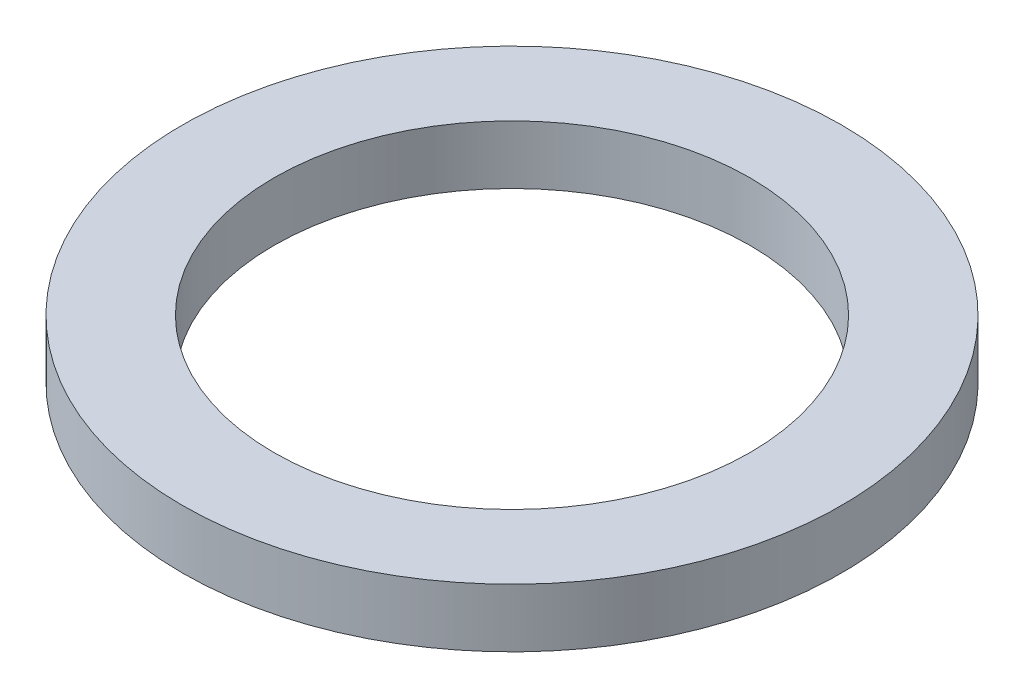
SolidWorks part; units mm, degrees
ref_plane "Front Plane" through (0, 0, 0) normal (0, 0, 1) x (1, 0, 0)
ref_plane "Top Plane" through (0, 0, 0) normal (0, 1, 0) x (1, 0, 0)
ref_plane "Right Plane" through (0, 0, 0) normal (1, 0, 0) x (0, 0, -1)
sketch "Sketch1" plane through (0, 0, 0) normal (0, 1, 0) x (1, 0, 0)
  circle A0 centre (0, 0) radius 45
  dimension "FLANGE_OD" = 90
extrude "Boss-Extrude1" add sketch "Sketch1" along normal blind 8
sketch "Sketch2" plane through (0, 0, 0) normal (0, 1, 0) x (1, 0, 0)
  circle A0 centre (0, 0) radius 32.5
  dimension "BORE_D" = 65
extrude "Cut-Extrude1" cut sketch "Sketch2" along normal through all
sketch "Sketch3" plane through (0, 8, 0) normal (0, 1, 0) x (1, 0, 0)
  circle A0 centre (0, 0) radius 20.2503 construction
  circle A1 centre (-20.2503, 0) radius 1.6744
  dimension "BOLT_D" = 3.3489
  dimension "BOLT_PCD" = 40.5006
extrude "Cut-Extrude2" cut sketch "Sketch3" against normal blind 4.9139 rebuild error yes
pattern_circular "CirPattern1" count 5 over 360 rebuild error yes
